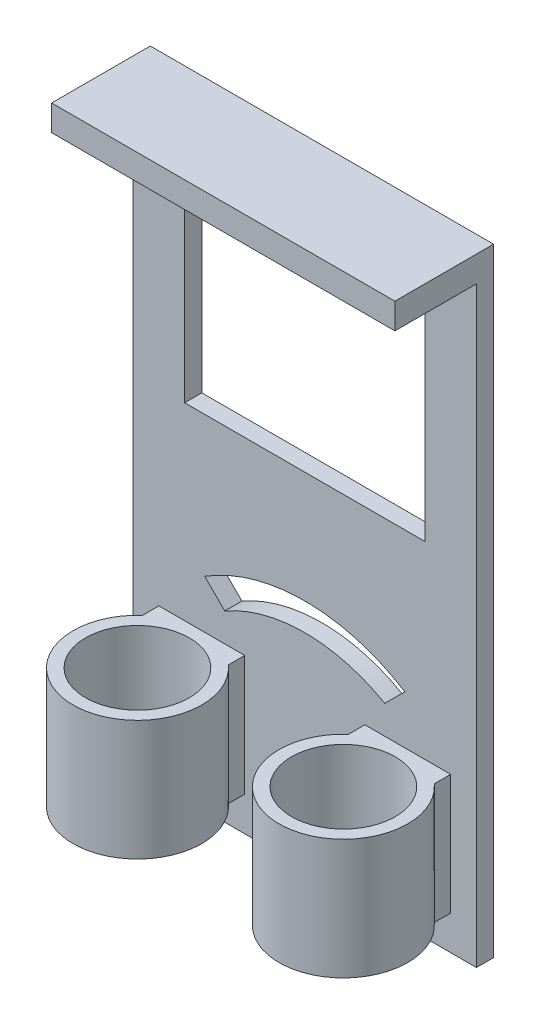
SolidWorks part; units mm, degrees
ref_plane "Front Plane" through (0, 0, 0) normal (0, 0, 1) x (1, 0, 0)
ref_plane "Top Plane" through (0, 0, 0) normal (0, 1, 0) x (1, 0, 0)
ref_plane "Right Plane" through (0, 0, 0) normal (1, 0, 0) x (0, 0, -1)
sketch "Sketch1" plane through (0, 0, 0) normal (0, 0, 1) x (1, 0, 0)
  line L1 (20, -20) -> (-20, -20)
  line L2 (20, -20) -> (20, 20)
  line L3 (20, 20) -> (-20, 20)
  line L4 (-20, -20) -> (-20, 20)
  line L5 (20, -20) -> (-20, 20) construction
  line L6 (20, 20) -> (-20, -20) construction
  point P0 (0, 0)
  dimension "D1" = 40
extrude "Boss-Extrude2" add sketch "Sketch1" along normal blind 2
sketch "Sketch2" plane through (0, 0, 2) normal (0, 0, 1) x (1, 0, 0)
  line L0 (-12, 0) -> (-12, 10) construction
  line L1 (0, 0) -> (-12, 0) construction
  line L2 (-15, 12) -> (-9, 12)
  line L3 (-15, 12) -> (-15, 8)
  line L4 (-15, 8) -> (-9, 8)
  line L5 (-9, 12) -> (-9, 8)
  line L6 (-15, 12) -> (-9, 8) construction
  line L7 (-15, 8) -> (-9, 12) construction
  point P1 (-12, 10)
  dimension "D1" = 10
  dimension "D2" = 4
  dimension "D3" = 6
  dimension "D4" = 12
extrude "Boss-Extrude5" add sketch "Sketch2" along normal blind 3
sketch "Sketch4" plane through (0, 12, 0) normal (0, 1, 0) x (1, 0, 0)
  line L1 (-9, -5) -> (-15, -5) construction
  circle A0 centre (-12, -6.6) radius 1.6
  circle A1 centre (-12, -6.6) radius 3.5
  point P9 (-12, -5)
  dimension "D1" = 3.2
  dimension "D2" = 7
  dimension "D3" = 1.6
extrude "Boss-Extrude6" add sketch "Sketch4" against normal blind 4
ref_plane "Plane2" through (0, 3, 0) normal (0, -1, 0) x (-1, 0, 0)
mirror "Mirror2" about plane through (0, 0, 0) normal (1, 0, 0) of "Boss-Extrude5", "Boss-Extrude6" second plane through (0, 3, 0) second plane normal (0, -1, 0)
sketch "Sketch6" plane through (0, 0, 2) normal (0, 0, 1) x (1, 0, 0)
  line L0 (-20, 20) -> (-15, 20)
  line L1 (20, 20) -> (-20, 20) construction
  line L2 (-15, 20) -> (-15, -20)
  line L3 (-20, -20) -> (20, -20) construction
  line L4 (-15, -20) -> (-20, -20)
  line L5 (-20, -20) -> (-20, 20)
  line L6 (20, 20) -> (15, 20)
  line L7 (15, 20) -> (15, -20)
  line L8 (15, -20) -> (20, -20)
  line L9 (20, -20) -> (20, 20)
  dimension "D1" = 5
  dimension "D2" = 5
  dimension "D4" = 5
extrude "Cut-Extrude1" [suppressed] cut sketch "Sketch6" against normal blind 3 contours L5 L0 L2 L4 | L9 L6 L7 L8
sketch "Sketch7" plane through (0, 0, 2) normal (0, 0, 1) x (1, 0, 0)
  line L0 (0, 0) -> (0, -15)
  line L1 (0, 0) -> (0, 7) construction
  line L2 (-8, 0) -> (8, 0) construction
  line L3 (9.3246, 1.3246) -> (11.6575, 3.6575)
  line L4 (-9.3246, 1.3246) -> (-11.6575, 3.6575)
  line L5 (-8, 0) -> (-9.3246, 1.3246) construction
  line L6 (8, 0) -> (9.3246, 1.3246) construction
  arc A0 (11.6575, 3.6575) -> (-11.6575, 3.6575) centre (0, -15) ccw
  arc A1 (9.3246, 1.3246) -> (-9.3246, 1.3246) centre (0, -15) ccw
  arc A2 (-9.3246, 1.3246) -> (9.3246, 1.3246) centre (0, -15) ccw construction
  arc A3 (-11.6575, 3.6575) -> (11.6575, 3.6575) centre (0, -15) ccw construction
  point P9 (0, 0)
  dimension "D1" = 15
  dimension "D2" = 7
  dimension "D3" = 3.2
  dimension "D4" = 8
  dimension "D5" = 45
  dimension "D6" = 45
extrude "Cut-Extrude2" cut sketch "Sketch7" against normal blind 2 contours A1 L3 A0 L4 region at (0, 4.477, 2)
sketch "Sketch8" plane through (0, 0, 0) normal (0, 0, -1) x (-1, 0, 0)
  line L0 (0, 0) -> (0, -10) construction
  circle A0 centre (0, -10) radius 1.6
  dimension "D1" = 10
  dimension "D2" = 3.2
extrude "Cut-Extrude3" cut sketch "Sketch8" against normal blind 2
sketch "Sketch18" plane through (0, 20, 0) normal (0, 1, 0) x (1, 0, 0)
  line L0 (20, -2) -> (-20, -2) construction
  line L1 (-20, 0) -> (-14, 0)
  line L2 (-20, 0) -> (-20, -2)
  line L3 (-20, -2) -> (-14, -2)
  line L4 (-14, 0) -> (-14, -2)
  line L6 (20, -2) -> (14, -2)
  line L7 (20, -2) -> (20, 0)
  line L8 (20, 0) -> (14, 0)
  line L9 (14, -2) -> (14, 0)
  line L10 (20, 0) -> (-20, 0) construction
  line M5 (20, 0) -> (-20, 0)
  line M6 (-20, 0) -> (-20, -2)
  line M7 (-20, -2) -> (20, -2)
  line M8 (20, -2) -> (20, 0)
  dimension "D2" = 6
  dimension "D1" = 6
extrude "Boss-Extrude10" add sketch "Sketch18" along normal blind 32 contours M7 M8 M5 | M6 M7 region at (-17, 20, 1) region at (17, 20, 1)
sketch "Sketch19" plane through (0, 52, 0) normal (0, 1, 0) x (1, 0, 0)
  line L13 (-20, 0) -> (20, 0)
  line L14 (-20, 0) -> (-20, -3.5)
  line L15 (-20, -3.5) -> (20, -3.5)
  line L16 (20, 0) -> (20, -3.5)
  line M10 (-14, 0) -> (-20, 0)
  line M11 (-20, 0) -> (-20, -2)
  line M12 (-20, -2) -> (-14, -2)
  dimension "D2" = 40
  dimension "D1" = 3.5
extrude "Boss-Extrude11" add sketch "Sketch19" against normal blind 3 contours M12 | M12 M10 M11 region at (0, 52, 1.75)
sketch "Sketch20" plane through (0, -6, 0) normal (0, -1, 0) x (1, 0, 0)
  line L3 (-9, 2) -> (-9, 4.7972)
  line L4 (-15, 4.7972) -> (-15, 2)
  line L5 (-15, 2) -> (-9, 2)
  line L6 (-9, 2) -> (-9, 4.7972)
  line L7 (-15, 4.7972) -> (-15, 2)
  line L8 (-15, 2) -> (-9, 2)
  line L9 (9, 4.7972) -> (9, 2)
  line L10 (9, 2) -> (15, 2)
  line L11 (15, 2) -> (15, 4.7972)
  line L12 (9, 4.7972) -> (9, 2)
  line L13 (9, 2) -> (15, 2)
  line L14 (15, 2) -> (15, 4.7972)
  circle A0 centre (-12, 6.6) radius 1.6 construction
  arc A1 (-9, 4.7972) -> (-15, 4.7972) centre (-12, 6.6) ccw
  arc A2 (-9, 4.7972) -> (-15, 4.7972) centre (-12, 6.6) ccw
  arc A3 (15, 4.7972) -> (9, 4.7972) centre (12, 6.6) ccw
  arc A4 (15, 4.7972) -> (9, 4.7972) centre (12, 6.6) ccw
  circle A5 centre (-12, 6.6) radius 1.6
  circle A6 centre (12, 6.6) radius 1.6 construction
  circle A7 centre (12, 6.6) radius 1.6
  dimension "D1" = 0
  dimension "D2" = 0
extrude "Boss-Extrude12" add sketch "Sketch20" along normal blind 10
sketch "Sketch21" plane through (0, 12, 0) normal (0, 1, 0) x (1, 0, 0)
  line L0 (9, -2) -> (9, -4.7972) construction
  line L1 (15, -4.7972) -> (15, -2) construction
  line L2 (15, -2) -> (9, -2) construction
  line L3 (-9, -4.7972) -> (-9, -2) construction
  line L4 (-9, -2) -> (-15, -2) construction
  line L5 (-15, -2) -> (-15, -4.7972) construction
  line L6 (9, -2) -> (9, -4.7972)
  line L7 (15, -4.7972) -> (15, -2)
  line L8 (15, -2) -> (9, -2)
  line L9 (-9, -4.7972) -> (-9, -2)
  line L10 (-9, -2) -> (-15, -2)
  line L11 (-15, -2) -> (-15, -4.7972)
  arc A0 (9, -4.7972) -> (15, -4.7972) centre (12, -6.6) ccw construction
  arc A1 (-15, -4.7972) -> (-9, -4.7972) centre (-12, -6.6) ccw construction
  circle A2 centre (-12, -6.6) radius 1.6 construction
  circle A3 centre (12, -6.6) radius 1.6 construction
  arc A4 (9, -4.7972) -> (15, -4.7972) centre (12, -6.6) ccw
  arc A5 (-15, -4.7972) -> (-9, -4.7972) centre (-12, -6.6) ccw
  circle A6 centre (-12, -6.6) radius 1.6
  circle A7 centre (12, -6.6) radius 1.6
sketch "Sketch22" plane through (0, -2, 0) normal (0, 1, 0) x (1, 0, 0)
  line L3 (9, -2) -> (9, -4.7972)
  line L4 (15, -4.7972) -> (15, -2)
  line L5 (15, -2) -> (9, -2)
  line L6 (9, -2) -> (9, -4.7972)
  line L7 (15, -4.7972) -> (15, -2)
  line L8 (15, -2) -> (9, -2)
  line L9 (-9, -4.7972) -> (-9, -2)
  line L10 (-9, -2) -> (-15, -2)
  line L11 (-15, -2) -> (-15, -4.7972)
  line L12 (-9, -4.7972) -> (-9, -2)
  line L13 (-9, -2) -> (-15, -2)
  line L14 (-15, -2) -> (-15, -4.7972)
  circle A0 centre (12, -6.6) radius 1.6 construction
  arc A1 (9, -4.7972) -> (15, -4.7972) centre (12, -6.6) ccw
  arc A2 (9, -4.7972) -> (15, -4.7972) centre (12, -6.6) ccw
  circle A3 centre (12, -6.6) radius 1.6
  circle A4 centre (-12, -6.6) radius 1.6 construction
  arc A5 (-15, -4.7972) -> (-9, -4.7972) centre (-12, -6.6) ccw
  arc A6 (-15, -4.7972) -> (-9, -4.7972) centre (-12, -6.6) ccw
  circle A7 centre (-12, -6.6) radius 1.6
  dimension "D1" = 0
  dimension "D2" = 0
extrude "Cut-Extrude4" cut sketch "Sketch22" against normal blind 7
sketch "Sketch23" plane through (0, -16, 0) normal (0, -1, 0) x (1, 0, 0)
  line L0 (-15, 2) -> (-9, 2) construction
  line L1 (-20, 2) -> (20, 2) construction
  line L2 (-15, 2) -> (-9, 2)
  line L3 (-17, 2) -> (-7, 2)
  line L4 (-7, 2) -> (-7, 3.9098)
  line L5 (-17, 2) -> (-17, 3.9098)
  line L6 (0, -5.555) -> (0, 5.555) construction
  line L7 (17, 2) -> (17, 3.9098)
  line L8 (7, 2) -> (7, 3.9098)
  line L9 (17, 2) -> (7, 2)
  line L10 (15, 2) -> (9, 2)
  circle A0 centre (-12, 9.5) radius 6.05
  arc A1 (-7, 3.9098) -> (-17, 3.9098) centre (-12, 9.5) ccw
  arc A2 (7, 3.9098) -> (17, 3.9098) centre (12, 9.5) cw
  circle A3 centre (12, 9.5) radius 6.05
  point P10 (-12, 2)
  point P11 (-12, 2)
  line M8 (-15, 2) -> (-9, 2)
  line M9 (-9, 2) -> (-9, 4.7972)
  line M11 (-15, 4.7972) -> (-15, 2)
  dimension "D1" = 12.1
  dimension "D2" = 15
  dimension "D3" = 10
extrude "Boss-Extrude14" add sketch "Sketch23" against normal blind 14 contours L4 A1 L5 L3 A0 M11 M9 | A0 M11 M8 M9 | A2 L8 L9 L7 A3 region at (-12, -16, 2.8701) region at (-16, -16, 2.2121) region at (16, -16, 2.2121)
extrude "Cut-Extrude5" cut sketch "Sketch21" against normal blind 10
sketch "Sketch24" plane through (0, -9, 0) normal (0, 1, 0) x (1, 0, 0)
  line L2 (9, -4.2462) -> (9, -4.7972)
  line L3 (15, -4.7972) -> (15, -4.2462)
  line L4 (9, -4.2462) -> (9, -4.7972)
  line L5 (15, -4.7972) -> (15, -4.2462)
  line L6 (-9, -4.7972) -> (-9, -4.2462)
  line L7 (-15, -4.2462) -> (-15, -4.7972)
  line L8 (-9, -4.7972) -> (-9, -4.2462)
  line L9 (-15, -4.2462) -> (-15, -4.7972)
  arc A2 (15, -4.2462) -> (9, -4.2462) centre (12, -9.5) ccw
  arc A3 (9, -4.7972) -> (15, -4.7972) centre (12, -6.6) ccw
  arc A4 (15, -4.2462) -> (9, -4.2462) centre (12, -9.5) ccw
  arc A5 (9, -4.7972) -> (15, -4.7972) centre (12, -6.6) ccw
  arc A6 (-9, -4.2462) -> (-15, -4.2462) centre (-12, -9.5) ccw
  arc A7 (-15, -4.7972) -> (-9, -4.7972) centre (-12, -6.6) ccw
  arc A8 (-9, -4.2462) -> (-15, -4.2462) centre (-12, -9.5) ccw
  arc A9 (-15, -4.7972) -> (-9, -4.7972) centre (-12, -6.6) ccw
  dimension "D1" = 0
  dimension "D2" = 0
extrude "Cut-Extrude7" cut sketch "Sketch24" against normal blind 22
sketch "Sketch25" plane through (0, -16, 0) normal (0, -1, 0) x (1, 0, 0)
  line L3 (-17, 2) -> (-7, 2)
  line L4 (-7, 2) -> (-7, 3.9098)
  line L5 (-17, 3.9098) -> (-17, 2)
  line L6 (-17, 2) -> (-7, 2)
  line L7 (-7, 2) -> (-7, 3.9098)
  line L8 (-17, 3.9098) -> (-17, 2)
  line L12 (7, 3.9098) -> (7, 2)
  line L13 (7, 2) -> (17, 2)
  line L14 (17, 2) -> (17, 3.9098)
  line L15 (7, 3.9098) -> (7, 2)
  line L16 (7, 2) -> (17, 2)
  line L17 (17, 2) -> (17, 3.9098)
  arc A1 (-7, 3.9098) -> (-17, 3.9098) centre (-12, 9.5) ccw
  arc A2 (-7, 3.9098) -> (-17, 3.9098) centre (-12, 9.5) ccw
  arc A4 (17, 3.9098) -> (7, 3.9098) centre (12, 9.5) ccw
  arc A5 (17, 3.9098) -> (7, 3.9098) centre (12, 9.5) ccw
  dimension "D1" = 0
  dimension "D2" = 0
sketch "Sketch26" plane through (0, -2, 0) normal (0, 1, 0) x (1, 0, 0)
  line L0 (-16, -2) -> (-8, -2) construction
  line L1 (-16, -2) -> (-16, -6.5)
  line L2 (-8, -2) -> (-8, -6.5)
  line L3 (-7, -2) -> (-17, -2)
  line L4 (-17, -2) -> (-17, -3.9098)
  line L5 (-7, -3.9098) -> (-7, -2)
  line L6 (-7, -2) -> (-17, -2)
  line L8 (-7, -3.9098) -> (-7, -2)
  line L9 (-16, -2) -> (-8, -2)
  line L10 (0, -9.35) -> (0, 9.35) construction
  line L11 (16, -2) -> (16, -6.5)
  line L12 (16, -2) -> (8, -2)
  line L13 (8, -2) -> (8, -6.5)
  circle A0 centre (-12, -9.5) radius 3.15
  arc A1 (-17, -3.9098) -> (-7, -3.9098) centre (-12, -9.5) ccw
  arc A3 (-16, -6.5) -> (-8, -6.5) centre (-12, -9.5) ccw
  circle A4 centre (12, -9.5) radius 3.15
  arc A5 (16, -6.5) -> (8, -6.5) centre (12, -9.5) cw
  point P10 (-12, -2)
  circle M14 centre (-12, -9.5) radius 6.05
  dimension "D2" = 6.3
  dimension "D3" = 10
  dimension "D4" = 4.5
  dimension "D1" = 0
extrude "Boss-Extrude17" [suppressed] add sketch "Sketch26" along normal blind 15 contours A5 L11 L12 L13 A4 | L1 A3 L2 A0 M14 | A3 L2 L9 L1 | A0
sketch "Sketch30" [suppressed] plane through (-20, 0, 0) normal (-1, 0, 0) x (0, 0, 1)
  line L1 (2, -6) -> (14.5, -6)
  line L2 (2, -6) -> (2, 4)
  line L3 (2, 4) -> (14.5, 4)
  line L4 (14.5, -6) -> (14.5, 4)
  line L5 (14.5, -6) -> (14.5, 9) construction
  dimension "D1" = 10
  dimension "D2" = 12.5
extrude "Cut-Extrude8" [suppressed] cut sketch "Sketch30" against normal blind 43
extrude "Cut-Extrude9" cut sketch "Sketch25" against normal blind 2
sketch "Sketch32" plane through (0, -14, 0) normal (0, -1, 0) x (1, 0, 0)
  line L3 (7, 3.9098) -> (7, 2)
  line L4 (7, 2) -> (17, 2)
  line L5 (17, 2) -> (17, 3.9098)
  line L6 (7, 3.9098) -> (7, 2)
  line L7 (7, 2) -> (17, 2)
  line L8 (17, 2) -> (17, 3.9098)
  line L9 (-17, 3.9098) -> (-17, 2)
  line L10 (-17, 2) -> (-7, 2)
  line L11 (-7, 2) -> (-7, 3.9098)
  line L12 (-17, 3.9098) -> (-17, 2)
  line L13 (-17, 2) -> (-7, 2)
  line L14 (-7, 2) -> (-7, 3.9098)
  circle A0 centre (-12, 9.5) radius 3.5
  arc A1 (17, 3.9098) -> (7, 3.9098) centre (12, 9.5) ccw
  arc A2 (17, 3.9098) -> (7, 3.9098) centre (12, 9.5) ccw
  arc A3 (-7, 3.9098) -> (-17, 3.9098) centre (-12, 9.5) ccw
  arc A4 (-7, 3.9098) -> (-17, 3.9098) centre (-12, 9.5) ccw
  circle A5 centre (12, 9.5) radius 3.5
  dimension "D3" = 7
  dimension "D4" = 7
  dimension "D1" = 0
  dimension "D2" = 0
extrude "Boss-Extrude19" add sketch "Sketch32" along normal blind 2
sketch "Sketch33" plane through (0, 0, 3.5) normal (0, 0, 1) x (1, 0, 0)
  line L4 (20, 52) -> (-20, 52)
  line L5 (-20, 52) -> (-20, 49)
  line L6 (-20, 49) -> (20, 49)
  line L7 (20, 49) -> (20, 52)
  line L8 (20, 52) -> (-20, 52)
  line L9 (-20, 52) -> (-20, 49)
  line L10 (-20, 49) -> (20, 49)
  line L11 (20, 49) -> (20, 52)
  dimension "D1" = 0
extrude "Boss-Extrude20" add sketch "Sketch33" along normal blind 8
